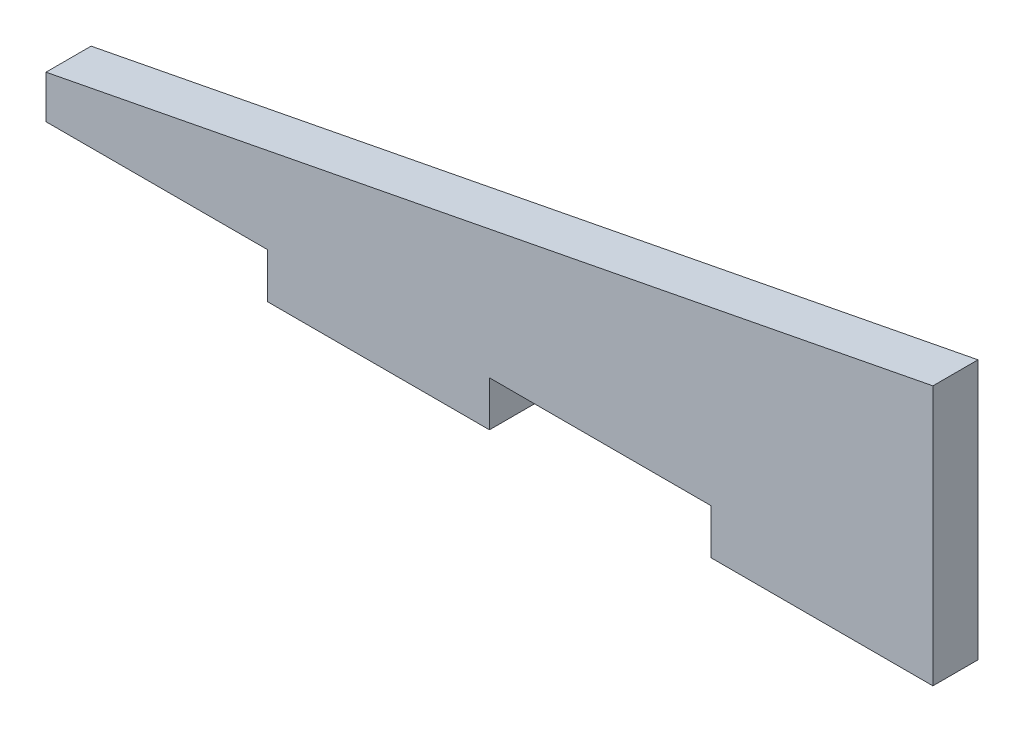
SolidWorks part; units mm, degrees
ref_plane "Front Plane" through (0, 0, 0) normal (0, 0, 1) x (1, 0, 0)
ref_plane "Top Plane" through (0, 0, 0) normal (0, 1, 0) x (1, 0, 0)
ref_plane "Right Plane" through (0, 0, 0) normal (1, 0, 0) x (0, 0, -1)
other "Center of Mass"
sketch "Sketch1" plane through (0, 0, 0) normal (0, 0, 1) x (1, 0, 0)
  line L1 (-57.0553, 21.5825) -> (47.8467, 21.5825)
  line L2 (-57.0553, 21.5825) -> (-57.0553, -9.1515)
  line L3 (-57.0553, -9.1515) -> (47.8467, -9.1515)
  line L4 (47.8467, 21.5825) -> (47.8467, -9.1515)
  dimension "D1" = 104.902
  dimension "D2" = 30.734
extrude "Boss-Extrude1" add sketch "Sketch1" along normal blind 5.334
sketch "Sketch2" plane through (0, 0, 5.334) normal (0, 0, 1) x (1, 0, 0)
  line L0 (-57.0553, -9.1515) -> (47.8467, -9.1515) construction
  line L1 (-57.0553, -9.1515) -> (-30.8298, -9.1515)
  line L2 (-57.0553, -9.1515) -> (-57.0553, -3.8175)
  line L3 (-57.0553, -3.8175) -> (-30.8298, -3.8175)
  line L4 (-30.8298, -9.1515) -> (-30.8298, -3.8175)
  line L5 (-4.6043, -9.1515) -> (21.6212, -9.1515)
  line L6 (-4.6043, -9.1515) -> (-4.6043, -3.8175)
  line L7 (-4.6043, -3.8175) -> (21.6212, -3.8175)
  line L8 (21.6212, -9.1515) -> (21.6212, -3.8175)
  line L9 (-30.8298, -3.8175) -> (-4.6043, -3.8175) construction
  line L10 (21.6212, -3.8175) -> (47.8467, -3.8175) construction
  line L11 (47.8467, -9.1515) -> (47.8467, 21.5825) construction
  dimension "D1" = 5.334
extrude "Cut-Extrude1" cut sketch "Sketch2" against normal through all
sketch "Sketch5" plane through (0, 0, 5.334) normal (0, 0, 1) x (1, 0, 0)
  line L0 (-57.0553, 1.2625) -> (47.8467, 21.5825)
  line L1 (-57.0553, 21.5825) -> (-57.0553, -3.8175) construction
  line L2 (47.8467, -9.1515) -> (47.8467, 21.5825) construction
  line L3 (21.6212, -3.8175) -> (-4.6043, -3.8175) construction
  line L5 (-57.0553, 1.2625) -> (-57.0553, 40.5148)
  line L6 (47.8467, 21.5825) -> (47.8467, 53.2148)
  line L7 (-57.0553, 40.5148) -> (47.8467, 53.2148)
  dimension "D1" = 5.08
  dimension "D2" = 25.4
extrude "Cut-Extrude4" cut sketch "Sketch5" against normal through all
equation "\"MDF\"= .21in"
equation "\"Foamcore\"= .13in"
equation "\"Gmaterial\"= \"MDF\""
equation "\"D2@Sketch1\"=\"MDF\"+1"
equation "\"D1@Boss-Extrude1\"=\"MDF\""
equation "\"D1@Sketch2\"=\"MDF\""
